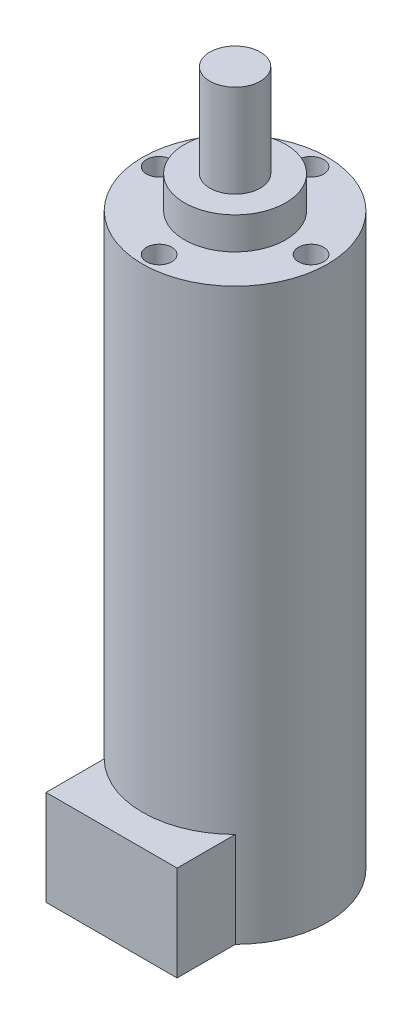
SolidWorks part; units mm, degrees
ref_plane "Front Plane" through (0, 0, 0) normal (0, 0, 1) x (1, 0, 0)
ref_plane "Top Plane" through (0, 0, 0) normal (0, 1, 0) x (1, 0, 0)
ref_plane "Right Plane" through (0, 0, 0) normal (1, 0, 0) x (0, 0, -1)
sketch "Sketch1" plane through (0, 0, 0) normal (0, 1, 0) x (1, 0, 0)
  circle A0 centre (0, 0) radius 10.9855
  dimension "D1" = 21.971
extrude "Boss-Extrude1" add sketch "Sketch1" along normal mid plane 67.6656
sketch "Sketch2" plane through (0, 33.8328, 0) normal (0, 1, 0) x (1, 0, 0)
  circle A0 centre (0, 0) radius 6.0071
  dimension "D1" = 12.0142
extrude "Boss-Extrude2" add sketch "Sketch2" along normal blind 3.81
sketch "Sketch3" plane through (0, 37.6428, 0) normal (0, 1, 0) x (1, 0, 0)
  circle A0 centre (0, 0) radius 2.9972
  dimension "D1" = 5.9944
extrude "Boss-Extrude3" add sketch "Sketch3" along normal blind 10.9982
sketch "Sketch4" plane through (0, 48.641, 0) normal (0, 1, 0) x (1, 0, 0)
  circle A0 centre (0, 0) radius 4.7625
  dimension "D1" = 9.525
sketch "Sketch5" plane through (0, 33.8328, 0) normal (0, 1, 0) x (1, 0, 0)
  circle A0 centre (0, 9.017) radius 1.5
  dimension "D1" = 3
  dimension "D2" = 9.017
extrude "Cut-Extrude1" cut sketch "Sketch5" against normal blind 7.62
pattern_circular "CirPattern1" count 4 over 360 about axis through (0, 33.8328, 0) along (0, 1, 0) of "Cut-Extrude1"
sketch "Sketch6" plane through (0, -33.8328, 0) normal (0, -1, 0) x (-1, 0, 0)
  line L2 (7.7776, -7.3062) -> (7.7776, -14.6648)
  line L3 (7.7776, -14.6648) -> (-7.7776, -14.6648)
  line L4 (-7.7776, -7.3062) -> (-7.7776, -14.6648)
  line L5 (7.7776, -7.3062) -> (-7.7776, -14.6648) construction
  line L6 (7.7776, -14.6648) -> (-7.7776, -7.3062) construction
  circle A0 centre (0, 0) radius 10.9855 construction
  circle A2 centre (0, 0) radius 10.9855
  circle A3 centre (0, 0) radius 10.9855
  point P0 (0, -10.9855)
  point P7 (-2.3317, 10.7352)
  circle M4 centre (0, 0) radius 10.9855
  dimension "D1" = 25.4
  dimension "D2" = 7.3586
  dimension "D3" = 15.5552
  dimension "D4" = 0
extrude "Boss-Extrude4" add sketch "Sketch6" against normal blind 11.303 contours L4 L3 L2 M4 region at (0, -33.8328, 12.23)
